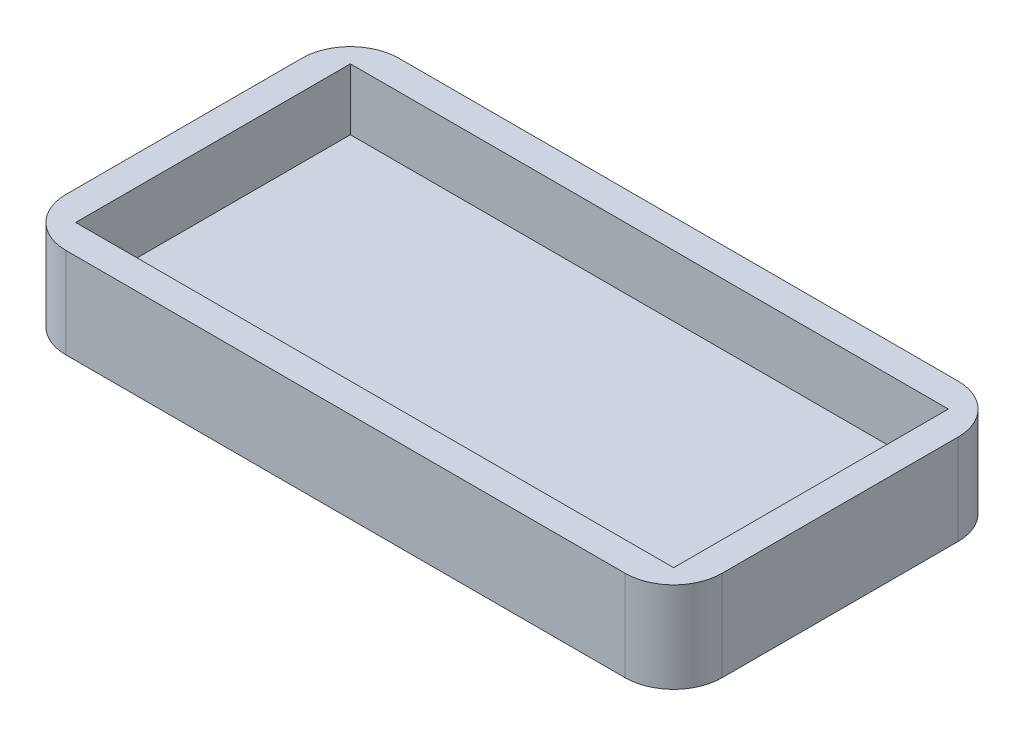
SolidWorks part; units mm, degrees
ref_plane "Front Plane" through (0, 0, 0) normal (0, 0, 1) x (1, 0, 0)
ref_plane "Top Plane" through (0, 0, 0) normal (0, 1, 0) x (1, 0, 0)
ref_plane "Right Plane" through (0, 0, 0) normal (1, 0, 0) x (0, 0, -1)
sketch "Croquis1" plane through (0, 0, 0) normal (0, 1, 0) x (1, 0, 0)
  line L1 (-18.5, -8.5) -> (18.5, -8.5)
  line L2 (-18.5, -8.5) -> (-18.5, 8.5)
  line L3 (-18.5, 8.5) -> (18.5, 8.5)
  line L4 (18.5, -8.5) -> (18.5, 8.5)
  line L5 (-18.5, -8.5) -> (18.5, 8.5) construction
  line L6 (-18.5, 8.5) -> (18.5, -8.5) construction
  point P0 (0, 0)
  dimension "D1" = 37
  dimension "D2" = 17
extrude "Saliente-Extruir1" add sketch "Croquis1" along normal blind 3.8
shell "Vaciado1" thickness 1.8 removed face at (0, 3.8, 0) outward yes
fillet "Redondeo2" radius 3 4 edges at (20.3, 1, -10.3) (20.3, 1, 10.3) (-20.3, 1, 10.3) (-20.3, 1, -10.3)
